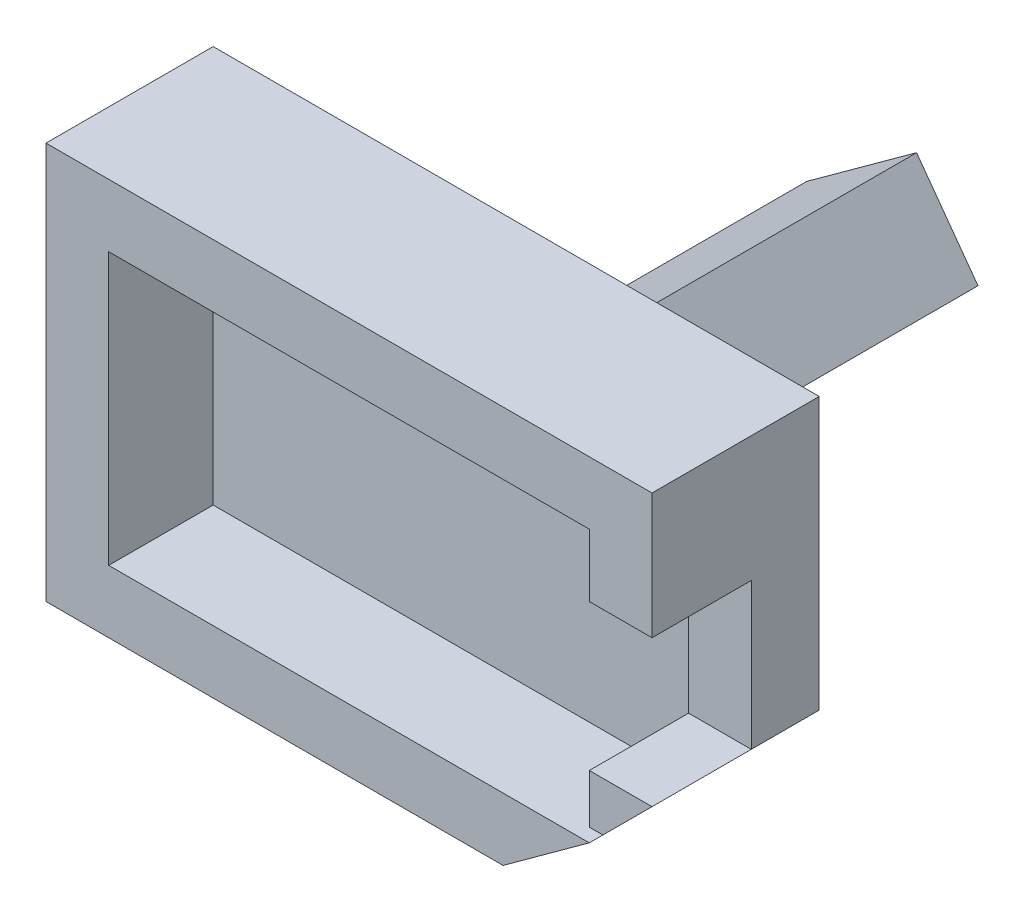
SolidWorks part; units mm, degrees
ref_plane "Front Plane" through (0, 0, 0) normal (0, 0, 1) x (1, 0, 0)
ref_plane "Top Plane" through (0, 0, 0) normal (0, 1, 0) x (1, 0, 0)
ref_plane "Right Plane" through (0, 0, 0) normal (1, 0, 0) x (0, 0, -1)
sketch "Sketch1" plane through (0, 0, 0) normal (0, 0, 1) x (1, 0, 0)
  line L0 (7.3709, -9.5) -> (-14.5, -9.5)
  line L1 (11.5, -6.5) -> (-11.5, -6.5) construction
  line L2 (11.5, -6.5) -> (11.5, 6.5) construction
  line L3 (11.5, 6.5) -> (-11.5, 6.5) construction
  line L4 (-11.5, -6.5) -> (-11.5, 6.5) construction
  line L5 (11.5, -6.5) -> (-11.5, 6.5) construction
  line L6 (11.5, 6.5) -> (-11.5, -6.5) construction
  line L7 (-14.5, -9.5) -> (-14.5, 9.5)
  line L8 (14.5, 9.5) -> (-14.5, 9.5)
  line L9 (14.5, -3.5) -> (14.5, 9.5)
  line L10 (14.5, -3.5) -> (11.5, -6.5)
  line L12 (7.3709, -9.5) -> (11.5, -6.5)
  line L13 (14.5, -9.5) -> (14.5, 9.5) construction
  line L14 (14.5, -9.5) -> (-14.5, -9.5) construction
  point P0 (0, 0)
  dimension "D1" = 13
  dimension "D2" = 23
  dimension "D4" = 45
  dimension "D5" = 36
  dimension "D3" = 3
extrude "Boss-Extrude1" add sketch "Sketch1" along normal blind 3
sketch "Sketch2" plane through (0, 0, 3) normal (0, 0, 1) x (1, 0, 0)
  line L0 (14.5, -3.5) -> (12.1512, -5.8488)
  line L1 (11.5, -6.5) -> (-11.5, -6.5)
  line L2 (11.5, -5.8488) -> (11.5, 6.5)
  line L3 (11.5, 6.5) -> (-11.5, 6.5)
  line L4 (-11.5, -6.5) -> (-11.5, 6.5)
  line L5 (11.5, -6.5) -> (-11.5, 6.5) construction
  line L6 (11.5, 6.5) -> (-11.5, -6.5) construction
  line L7 (7.3709, -9.5) -> (-14.5, -9.5)
  line L8 (14.5, -3.5) -> (14.5, 9.5)
  line L9 (14.5, 9.5) -> (-14.5, 9.5)
  line L10 (-14.5, -9.5) -> (-14.5, 9.5)
  line L11 (14.5, -9.5) -> (-14.5, 9.5) construction
  line L12 (14.5, 9.5) -> (-14.5, -9.5) construction
  line L13 (11.5, -5.8488) -> (12.1512, -5.8488)
  line L14 (11.5, -6.5) -> (7.3709, -9.5)
  point P0 (0, 0)
  point P7 (0, 0)
  dimension "D1" = 2.3488
  dimension "D2" = 45
  dimension "D3" = 13
  dimension "D4" = 5.1039
extrude "Boss-Extrude2" add sketch "Sketch2" along normal blind 5
sketch "Sketch3" plane through (0, 0, 0) normal (0, 0, -1) x (-1, 0, 0)
  line L0 (0, 0) -> (5.8546, 0) construction
  line L1 (-1.1598, 3.9328) -> (4.0988, 0.1122)
  line L2 (-1.1598, 3.9328) -> (-4.0988, -0.1122)
  line L3 (-4.0988, -0.1122) -> (1.1598, -3.9328)
  line L4 (4.0988, 0.1122) -> (1.1598, -3.9328)
  line L5 (-1.1598, 3.9328) -> (1.1598, -3.9328) construction
  line L6 (-4.0988, -0.1122) -> (4.0988, 0.1122) construction
  line L7 (0, 0) -> (4.1972, -3.0495) construction
  point P0 (0, 0)
  dimension "D1" = 36
  dimension "D2" = 5
  dimension "D3" = 5.188
  dimension "D4" = 6.5
extrude "Boss-Extrude3" add sketch "Sketch3" along normal blind 18
sketch "Sketch4" plane through (14.5, 0, 0) normal (1, 0, 0) x (0, 0, -1)
  line L0 (0, 0) -> (-4, 0) construction
  line L1 (-8, 3.5) -> (-8, -3.5)
  line L2 (-3.25, -3.5) -> (-8, -3.5)
  line L3 (-3.25, -3.5) -> (-3.25, 3.5)
  line L4 (-3.25, 3.5) -> (-8, 3.5)
  dimension "D1" = 4
  dimension "D2" = 0.75
  dimension "D3" = 7
  dimension "D4" = 4.75
extrude "Cut-Extrude1" cut sketch "Sketch4" against normal blind 8
